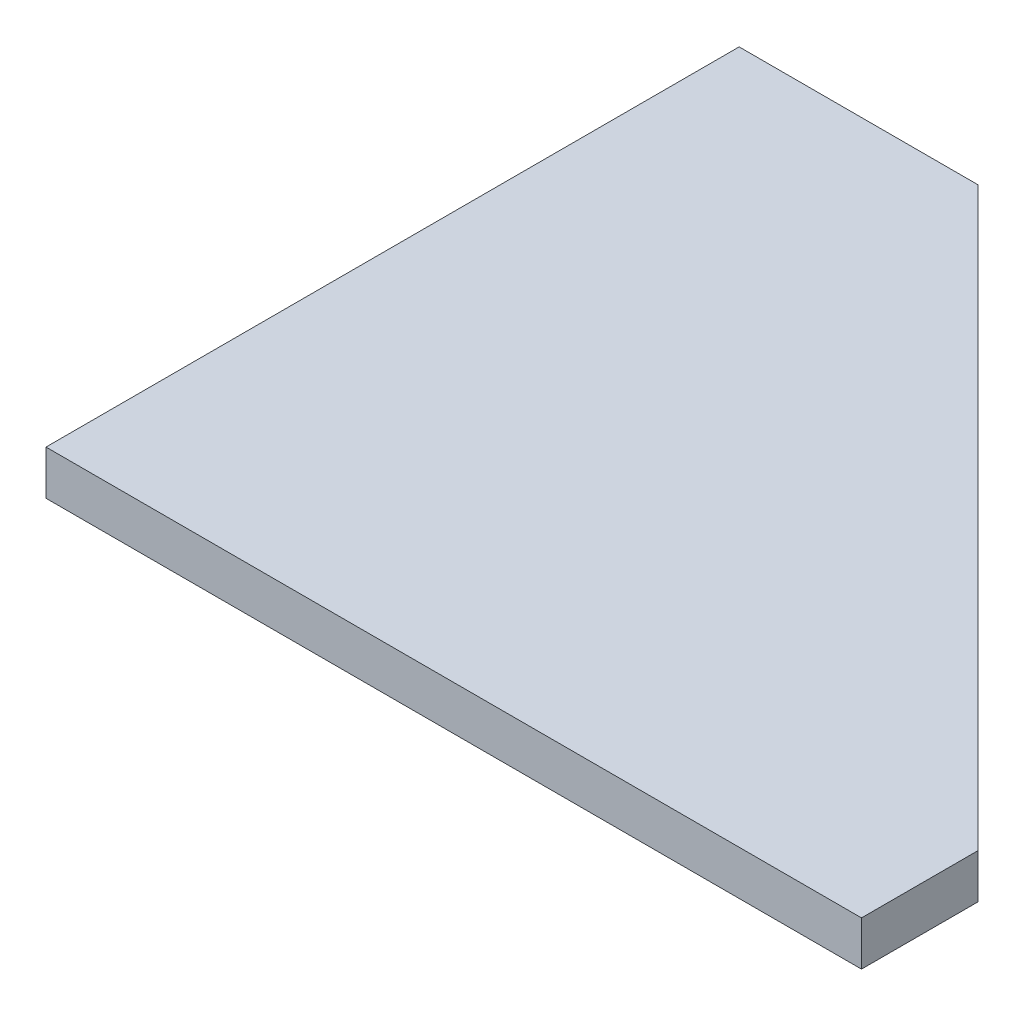
SolidWorks part; units mm, degrees
ref_plane "Front Plane" through (0, 0, 0) normal (0, 0, 1) x (1, 0, 0)
ref_plane "Top Plane" through (0, 0, 0) normal (0, 1, 0) x (1, 0, 0)
ref_plane "Right Plane" through (0, 0, 0) normal (1, 0, 0) x (0, 0, -1)
sketch "Sketch1" plane through (0, 0, 0) normal (0, 1, 0) x (1, 0, 0)
  line L0 (-144.97, 297.485) -> (350, -197.485)
  line L1 (-350, 297.485) -> (-144.97, 297.485)
  line L2 (-350, 297.485) -> (-350, -297.485)
  line L3 (-350, -297.485) -> (350, -297.485)
  line L4 (350, -197.485) -> (350, -297.485)
  line L5 (-350, 297.485) -> (350, -297.485) construction
  point P0 (0, 0)
  point P4 (-136.2391, 290.0641)
  dimension "D1" = 594.97
  dimension "D2" = 700
  dimension "D3" = 100
  dimension "D4" = 45
extrude "Boss-Extrude1" add sketch "Sketch1" along normal blind 38.1
sketch "Sketch2" plane through (0, 0, 0) normal (0, -1, 0) x (1, 0, 0)
  line L5 (-350, -297.485) -> (-350, 297.485) construction
  line L6 (-350, -107.485) -> (-331, -107.485)
  line L7 (-350, -107.485) -> (-350, -157.485)
  line L8 (-350, -157.485) -> (-331, -157.485)
  line L9 (-331, -107.485) -> (-331, -157.485)
  line L10 (-144.97, -297.485) -> (-350, -297.485) construction
  line L11 (-350, 0) -> (152.515, 0) construction
  line L12 (350, 197.485) -> (-144.97, -297.485) construction
  line L13 (-331, 107.485) -> (-331, 157.485)
  line L14 (-350, 157.485) -> (-331, 157.485)
  line L15 (-350, 107.485) -> (-350, 157.485)
  line L16 (-350, 107.485) -> (-331, 107.485)
  dimension "D1" = 50
  dimension "D2" = 19
  dimension "D3" = 140
extrude "Cut-Extrude1" cut sketch "Sketch2" against normal blind 2
